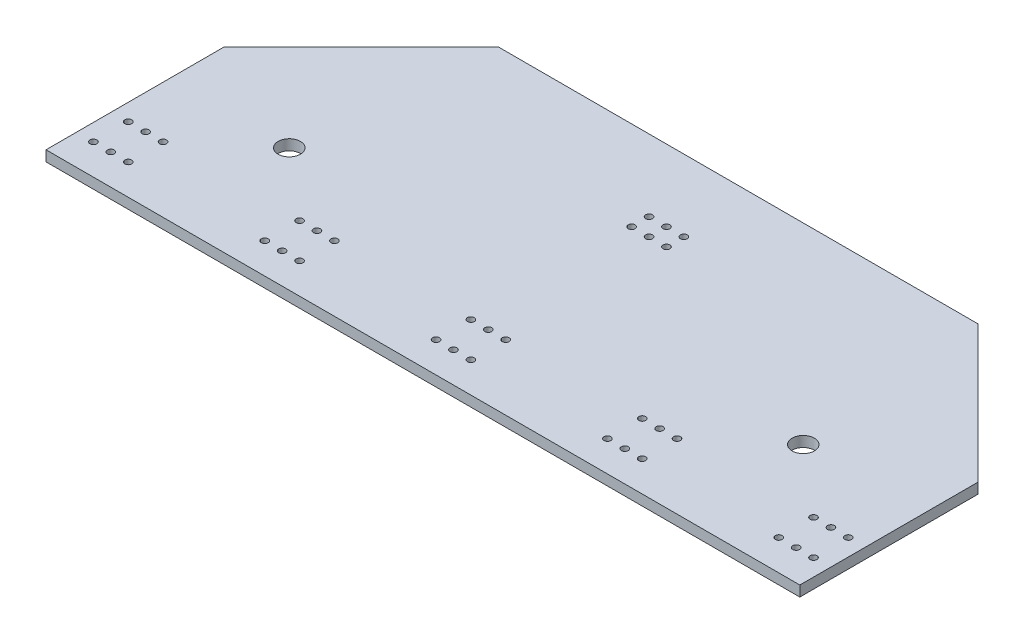
SolidWorks part; units mm, degrees
ref_plane "Front Plane" through (0, 0, 0) normal (0, 0, 1) x (1, 0, 0)
ref_plane "Top Plane" through (0, 0, 0) normal (0, 1, 0) x (1, 0, 0)
ref_plane "Right Plane" through (0, 0, 0) normal (1, 0, 0) x (0, 0, -1)
sketch "Sketch1" plane through (0, 0, 0) normal (0, 1, 0) x (1, 0, 0)
  line L0 (0, 0) -> (0, 13) construction
  line L1 (-55, -22) -> (55, -22)
  line L2 (-55, -22) -> (-55, 28)
  line L3 (-55, 28) -> (55, 28)
  line L4 (55, -22) -> (55, 28)
  line L5 (0, 0) -> (55, 28) construction
  line L6 (-55, 28) -> (0, 0) construction
  line L11 (0, 13) -> (0, 28) construction
  point P0 (0, 0)
  dimension "D1" = 110
  dimension "D2" = 28
  dimension "D6" = 22
extrude "Boss-Extrude1" add sketch "Sketch1" along normal blind 1.53
sketch "Sketch6" plane through (0, 1.53, 0) normal (0, 1, 0) x (1, 0, 0)
  line L0 (-35, 28) -> (-55, 8)
  line L1 (55, 28) -> (-55, 28) construction
  line L2 (-55, 28) -> (-55, -22) construction
  line L3 (-55, 8) -> (-55, -18)
  line L5 (-55, -22) -> (55, -22) construction
  line L6 (-52, -22) -> (-28, -22)
  line L8 (-55, -18) -> (55, -18)
  line L12 (55, -22) -> (55, 28) construction
  line L13 (55, -18) -> (55, 8)
  line L14 (55, 8) -> (35, 28)
  line L15 (35, 28) -> (-35, 28)
  line L16 (0, 0) -> (0, -18) construction
  line L17 (0, 0) -> (0, 28) construction
  line L18 (-70.5255, 34.7658) -> (-70.5255, -34.7658)
  line L23 (-70.5255, -34.7658) -> (70.5255, 34.7658) construction
  line L24 (-70.5255, 34.7658) -> (70.5255, -34.7658) construction
  line L25 (-70.5255, -34.7658) -> (70.5255, -34.7658)
  line L26 (70.5255, -34.7658) -> (70.5255, 34.7658)
  line L27 (70.5255, 34.7658) -> (-70.5255, 34.7658)
  line M37 (55, -22) -> (55, 28)
  line M38 (55, 28) -> (-55, 28)
  line M39 (-55, 28) -> (-55, -22)
  line M40 (-55, -22) -> (55, -22)
  dimension "D1" = 45
  dimension "D2" = 26
  dimension "D5" = 18
extrude "Cut-Extrude4" cut sketch "Sketch6" against normal through all contours L26 L27 L18 L25 M37 M40 M39 M38 | L8 M39 M40 M37 | L0 M38 M39 | L14 M37 M38 region at (-48.3333, 1.53, -21.3333) region at (48.3333, 1.53, -21.3333) region at (0, 1.53, 20) region at (0, 1.53, -33.1932)
sketch "Sketch2" plane through (0, 1.53, 0) normal (0, 1, 0) x (1, 0, 0)
  line L0 (0, -11) -> (4.8827, -11) construction
  line L3 (-55, -18) -> (55, -18) construction
  line L24 (-2.54, -8.46) -> (0, -8.46) construction
  line L25 (0, -8.46) -> (2.54, -8.46) construction
  line L26 (0, -8.46) -> (0, -13.54) construction
  line L27 (0, -13.54) -> (2.54, -13.54) construction
  line L28 (0, -13.54) -> (-2.54, -13.54) construction
  line L29 (0, -8.46) -> (0, 0) construction
  circle A25 centre (-2.54, -8.46) radius 0.5
  circle A26 centre (0, -8.46) radius 0.5
  circle A27 centre (2.54, -8.46) radius 0.5
  circle A28 centre (-2.54, -13.54) radius 0.5
  circle A29 centre (0, -13.54) radius 0.5
  circle A30 centre (2.54, -13.54) radius 0.5
  dimension "D1" = 7
  dimension "D2" = 1
  dimension "D8" = 5.08
  dimension "D9" = 2.54
extrude "PushButtonHoles" cut sketch "Sketch2" against normal through all
sketch "Sketch7" plane through (0, 1.53, 0) normal (0, 1, 0) x (1, 0, 0)
  line L0 (-37.5, 0) -> (0, 0) construction
  line L1 (0, 0) -> (37.5, 0) construction
  line L3 (-55, 8) -> (-55, -18) construction
  line L4 (55, -18) -> (55, 8) construction
  line L5 (-55, -18) -> (55, -18) construction
  circle A0 centre (-37.5, 0) radius 1.625
  circle A1 centre (37.5, 0) radius 1.625
  dimension "D1" = 3.25
  dimension "D3" = 18
  dimension "D4" = 17.5
  dimension "D5" = 75
  dimension "D6" = 17.5
  dimension "D2" = 37.5
extrude "Mount Holes" cut sketch "Sketch7" against normal through all
sketch "Sketch5" plane through (0, 1.53, 0) normal (0, 1, 0) x (1, 0, 0)
  line L0 (-2.54, 17.54) -> (0, 17.54) construction
  line L1 (0, 17.54) -> (2.54, 17.54) construction
  line L2 (0, 17.54) -> (0, 15) construction
  line L3 (0, 15) -> (2.54, 15) construction
  line L4 (0, 15) -> (-2.54, 15) construction
  line L5 (0, 0) -> (0, 15) construction
  circle A0 centre (-2.54, 17.54) radius 0.5
  circle A1 centre (0, 17.54) radius 0.5
  circle A2 centre (2.54, 17.54) radius 0.5
  circle A3 centre (-2.54, 15) radius 0.5
  circle A4 centre (0, 15) radius 0.5
  circle A5 centre (2.54, 15) radius 0.5
  dimension "D1" = 2.54
  dimension "D2" = 2.54
  dimension "D3" = 15
extrude "RJ12Holes" cut sketch "Sketch5" against normal through all
pattern_linear "LPattern1" count 3 spacing 25 along (1, 0, 0) count 3 spacing 25 along (-1, 0, 0) of "PushButtonHoles" pattern seed only yes
